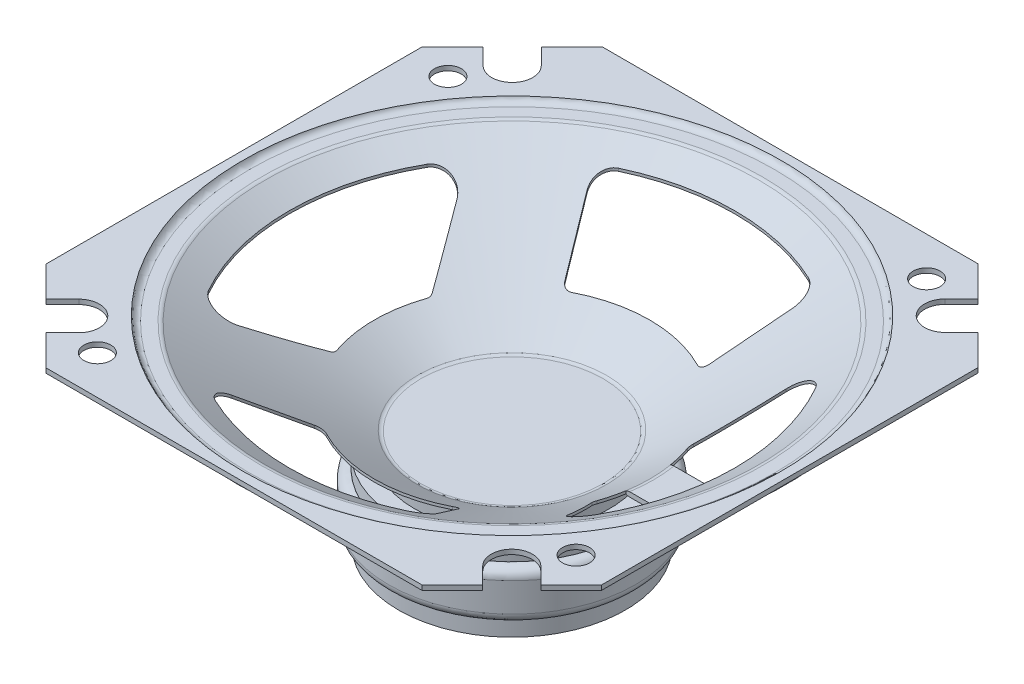
SolidWorks part; units mm, degrees
ref_plane "Front Plane" through (0, 0, 0) normal (0, 0, 1) x (1, 0, 0)
ref_plane "Top Plane" through (0, 0, 0) normal (0, 1, 0) x (1, 0, 0)
ref_plane "Right Plane" through (0, 0, 0) normal (1, 0, 0) x (0, 0, -1)
sketch "Sketch7" plane through (0, 0, 0) normal (0, 0, 1) x (1, 0, 0)
  line L0 (0, 0) -> (0, 80.3345) construction
  line L1 (17.2339, 0) -> (18.0594, 0)
  line L2 (18.0594, 0) -> (45.5151, 16.8148)
  line L3 (45.5151, 16.8148) -> (50.7873, 16.8148)
  line L4 (50.7873, 16.8148) -> (50.7873, 17.6403)
  line L5 (17.2339, 0) -> (46.0375, 17.6403)
  line L6 (46.0375, 17.6403) -> (50.7873, 17.6403)
  dimension "D1" = 18.0594
  dimension "D2" = 4.7498
  dimension "D3" = 16.8148
  dimension "D4" = 50.7873
  dimension "D5" = 0.8255
  dimension "D6" = 0
  dimension "D7" = 0.8255
revolve "Revolve2" add sketch "Sketch7" angle 360 about L0
sketch "Sketch9" plane through (0, 0, 0) normal (0, -1, 0) x (1, 0, 0)
  circle A1 centre (0, 0) radius 18.0594
extrude "Boss-Extrude2" add sketch "Sketch9" along normal blind 3.4417
sketch "Sketch10" plane through (0, -3.4417, 0) normal (0, -1, 0) x (1, 0, 0)
  circle A0 centre (0, 0) radius 21.0947
  dimension "D1" = 42.1894
extrude "Boss-Extrude3" add sketch "Sketch10" along normal blind 2.6162
sketch "Sketch11" plane through (0, -6.0579, 0) normal (0, -1, 0) x (1, 0, 0)
  circle A0 centre (0, 0) radius 22.8981
  dimension "D1" = 45.7962
extrude "Boss-Extrude4" add sketch "Sketch11" along normal blind 8.9154
sketch "Sketch12" plane through (0, -14.9733, 0) normal (0, -1, 0) x (1, 0, 0)
  circle A0 centre (0, 0) radius 21.0185
  dimension "D1" = 42.037
extrude "Boss-Extrude5" add sketch "Sketch12" along normal blind 3.2512
fillet "Fillet1" radius 1.778 2 edges at (0, -6.0579, -22.8981) (0, -14.9733, -22.8981)
fillet "Fillet2" radius 1.778 1 edges at (0, 0, -18.0594)
sketch "Sketch13" plane through (0, 17.6403, 0) normal (0, 1, 0) x (1, 0, 0)
  line L1 (12.7667, 22.1125) -> (20.647, 35.7617)
  line L2 (-12.7667, 22.1125) -> (-20.647, 35.7617)
  line L3 (12.7667, -22.1125) -> (20.647, -35.7617)
  line L4 (-12.7667, -22.1125) -> (-20.647, -35.7617)
  arc A0 (12.7667, 22.1125) -> (-12.7667, 22.1125) centre (0, 0) ccw
  arc A1 (20.647, 35.7617) -> (-20.647, 35.7617) centre (0, 0) ccw
  arc A2 (-12.7667, -22.1125) -> (12.7667, -22.1125) centre (0, 0) ccw
  arc A3 (-20.647, -35.7617) -> (20.647, -35.7617) centre (0, 0) ccw
  dimension "D1" = 51.0667
  dimension "D2" = 82.5881
extrude "Cut-Extrude1" cut sketch "Sketch13" against normal blind 16.9672
fillet "Fillet3" radius 3.175 4 edges at (20.647, 14.4825, 35.7617) (-20.647, 14.4825, 35.7617) (-20.647, 14.4825, -35.7617) (20.647, 14.4825, -35.7617)
fillet "Fillet4" radius 1.27 4 edges at (12.7667, 4.8301, -22.1125) (-12.7667, 4.8301, -22.1125) (12.7667, 4.8301, 22.1125) (-12.7667, 4.8301, 22.1125)
sketch "Sketch14" plane through (0, 17.6403, 0) normal (0, 1, 0) x (1, 0, 0)
  line L0 (33.058, 24.7461) -> (23.9231, 8.924)
  line L1 (33.058, -24.7461) -> (23.9231, -8.924)
  line L2 (-23.9231, -8.924) -> (-33.058, -24.7461)
  line L3 (-33.058, 24.7461) -> (-23.9231, 8.924)
  arc A0 (33.058, -24.7461) -> (33.058, 24.7461) centre (0, 0) ccw
  arc A1 (23.9231, -8.924) -> (23.9231, 8.924) centre (0, 0) ccw
  arc A2 (-23.9231, 8.924) -> (-23.9231, -8.924) centre (0, 0) ccw
  arc A3 (-33.058, 24.7461) -> (-33.058, -24.7461) centre (0, 0) ccw
extrude "Cut-Extrude2" cut sketch "Sketch14" against normal blind 16.9672
fillet "Fillet5" radius 3.175 4 edges at (-33.058, 14.4825, -24.7461) (-33.058, 14.4825, 24.7461) (33.058, 14.4825, 24.7461) (33.058, 14.4825, -24.7461)
fillet "Fillet6" radius 1.27 4 edges at (-23.9231, 4.8301, 8.924) (-23.9231, 4.8301, -8.924) (23.9231, 4.8301, 8.924) (23.9231, 4.8301, -8.924)
sketch "Sketch15" plane through (0, 17.6403, 0) normal (0, 1, 0) x (1, 0, 0)
  line L0 (36.5697, 4.1148) -> (36.5697, -4.1148)
  line L3 (36.5697, -4.1148) -> (25.1996, -4.1148)
  line L4 (36.5697, 4.1148) -> (25.1996, 4.1148)
  arc A0 (24.1181, -8.3826) -> (24.1181, 8.3826) centre (0, 0) ccw construction
  arc A1 (25.1996, -4.1148) -> (25.1996, 4.1148) centre (0, 0) ccw
extrude "Boss-Extrude6" add sketch "Sketch15" against normal blind 13.208
fillet "Fillet7" radius 1.27 1 edges at (25.5334, 4.4323, 0)
sketch "Sketch16" plane through (0, 0, 4.1148) normal (0, 0, 1) x (1, 0, 0)
  line L0 (36.5697, 5.2959) -> (25.1996, 5.2959)
  line L1 (36.5697, 4.4323) -> (36.5697, 17.6403) construction
  line L2 (25.1996, 5.0829) -> (25.1996, 17.6403) construction
  line L3 (25.7965, 4.4323) -> (36.5697, 4.4323) construction
  line L4 (36.5697, 5.2959) -> (36.5697, 17.6403)
  line L5 (25.1996, 5.2959) -> (25.1996, 17.6403)
  line L6 (25.1996, 17.6403) -> (36.5697, 17.6403)
  dimension "D1" = 0
  dimension "D2" = 0.8636
extrude "Cut-Extrude3" cut sketch "Sketch16" against normal blind 10.668
fillet "Fillet8" radius 1.27 1 edges at (25.5334, 5.2959, 0)
sketch "Sketch17" plane through (0, 17.6403, 0) normal (0, 1, 0) x (1, 0, 0)
  line L1 (-51.4985, -51.5366) -> (51.4985, -51.5366)
  line L2 (-51.4985, -51.5366) -> (-51.4985, 51.5366)
  line L3 (-51.4985, 51.5366) -> (51.4985, 51.5366)
  line L4 (51.4985, -51.5366) -> (51.4985, 51.5366)
  line L5 (-51.4985, -51.5366) -> (51.4985, 51.5366) construction
  line L6 (-51.4985, 51.5366) -> (51.4985, -51.5366) construction
  circle A0 centre (0, 0) radius 49.8983
  circle A1 centre (0, 0) radius 50.7873 construction
  dimension "D1" = 0.889
  dimension "D2" = 102.997
  dimension "D3" = 103.0732
extrude "Boss-Extrude7" add sketch "Sketch17" along normal blind 0.8763
chamfer "Chamfer1" distance 16.6624 angle 45 4 edges at (51.4985, 18.0784, -51.5366) (-51.4985, 18.0784, -51.5366) (-51.4985, 18.0784, 51.5366) (51.4985, 18.0784, 51.5366)
sketch "Sketch18" plane through (0, 18.5166, 0) normal (0, 1, 0) x (1, 0, 0)
  line L1 (-51.4985, -34.8742) -> (-34.8361, -51.5366) construction
  line L2 (51.4985, 34.8742) -> (34.8361, 51.5366) construction
  line L3 (-40.4732, 45.8995) -> (-37.4379, 42.8642)
  line L4 (-34.8361, 51.5366) -> (-51.4985, 34.8742) construction
  line L5 (34.8361, -51.5366) -> (51.4985, -34.8742) construction
  line L8 (-43.1673, 43.2054) -> (-40.4732, 45.8995)
  line L9 (-43.1673, 43.2054) -> (-45.8638, 40.5137)
  line L10 (43.1673, -43.2054) -> (45.8614, -40.5113)
  line L11 (43.1673, -43.2054) -> (40.4732, -45.8995)
  line L12 (-43.1673, -43.2054) -> (-40.4732, -45.8995)
  line L13 (-43.1673, -43.2054) -> (-45.8614, -40.5113)
  line L14 (45.8614, -40.5113) -> (42.8261, -37.476)
  line L15 (40.4732, -45.8995) -> (37.4379, -42.8642)
  line L17 (-40.4732, -45.8995) -> (-37.4379, -42.8642)
  line L18 (-45.8614, -40.5113) -> (-42.8261, -37.476)
  line L19 (-45.8638, 40.5137) -> (-42.8311, 37.4757)
  line L20 (40.4708, 45.8971) -> (37.4382, 42.8591)
  line L21 (45.8614, 40.5113) -> (42.8261, 37.476)
  line L25 (40.4708, 45.8971) -> (40.5268, 45.9531)
  line L26 (40.5268, 45.9531) -> (46.098, 40.7709)
  line L27 (46.098, 40.7709) -> (45.8614, 40.5113)
  arc A0 (-37.4379, -42.8642) -> (-42.8261, -37.476) centre (-40.132, -40.1701) ccw
  arc A1 (-42.8317, 37.4763) -> (-37.4391, 42.8653) centre (-40.1339, 40.1693) ccw
  arc A2 (37.4382, 42.8591) -> (42.8261, 37.476) centre (40.1321, 40.1675) ccw
  arc A3 (42.8261, -37.476) -> (37.4379, -42.8642) centre (40.132, -40.1701) ccw
  dimension "D2" = 3.81
  dimension "D3" = 3.81
  dimension "D4" = 3.81
  dimension "D5" = 90
  dimension "D6" = 4.2926
  dimension "D7" = 4.2926
  dimension "D8" = 90
  dimension "D9" = 4.2926
  dimension "D10" = 4.2926
  dimension "D11" = 4.2926
  dimension "D12" = 4.2926
extrude "Cut-Extrude4" cut sketch "Sketch18" against normal blind 0.8763
sketch "Sketch19" plane through (0, 17.6403, 0) normal (0, -1, 0) x (1, 0, 0)
  line L1 (-34.8361, 51.5366) -> (34.8361, 51.5366) construction
  circle A0 centre (44.3611, 32.4866) radius 2.4955
  circle A1 centre (32.4866, -44.3611) radius 2.4955
  circle A2 centre (-44.3611, -32.4866) radius 2.4956
  circle A3 centre (-32.4866, 44.3611) radius 2.4956
  point P15 (0, 0)
  dimension "D1" = 4.9911
  dimension "D2" = 19.05
  dimension "D3" = 9.525
  dimension "D4" = 4
extrude "Cut-Extrude5" cut sketch "Sketch19" against normal up to next and the other way through all
fillet "Fillet9" radius 1.27 1 edges at (0, 17.6403, 49.8983)
fillet "Fillet10" radius 1.27 1 edges at (0, 17.6403, -46.0375)
fillet "Fillet11" radius 1.27 1 edges at (0, 0, -17.2339)
fillet "Fillet12" radius 1.27 2 edges at (36.5697, 4.8641, -4.1148) (36.5697, 4.8641, 4.1148)
